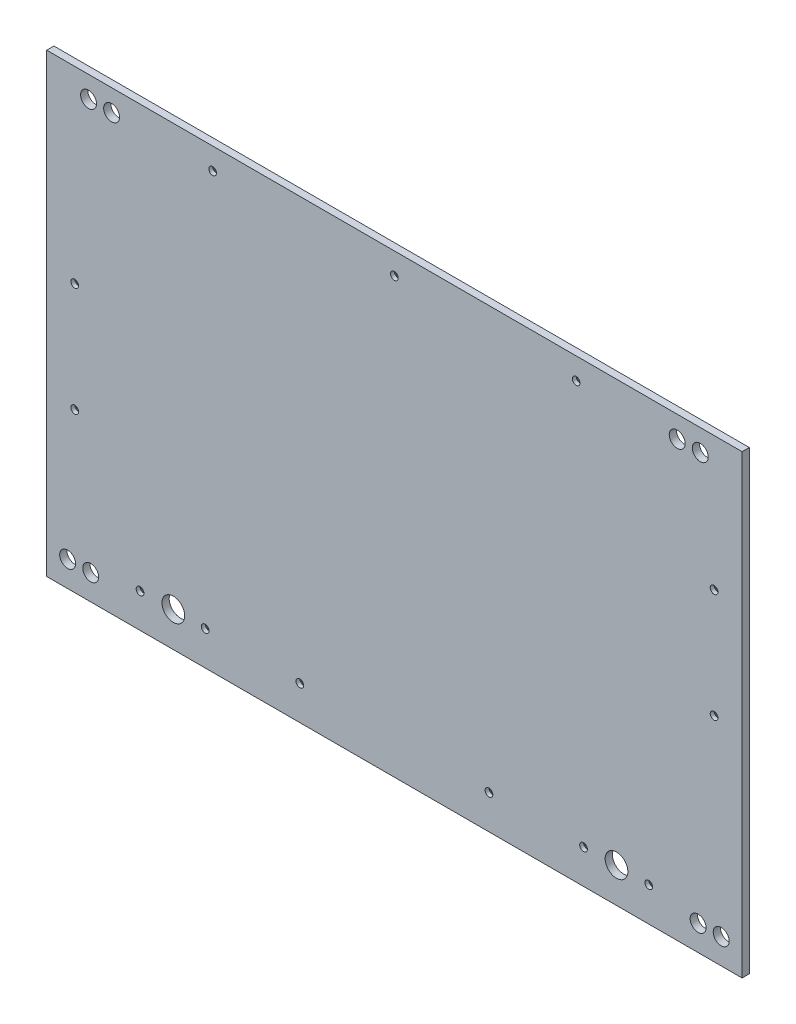
SolidWorks part; units mm, degrees
material "ABS"
ref_plane "X-Y Datum" through (0, 0, 0) normal (0, 0, 1) x (1, 0, 0)
ref_plane "X-Z Datum" through (0, 0, 0) normal (0, 1, 0) x (1, 0, 0)
ref_plane "Y-Z Datum" through (0, 0, 0) normal (1, 0, 0) x (0, 0, -1)
sketch "Sketch1" plane through (0, 0, 0) normal (0, 0, 1) x (1, 0, 0)
  line L0 (-153.025, 98.7125) -> (-153.025, -98.7125)
  line L1 (-153.025, 98.7125) -> (153.025, 98.7125)
  line L2 (-153.025, 98.7125) -> (-153.025, -98.7125)
  line L3 (-153.025, -98.7125) -> (153.025, -98.7125)
  line L4 (153.025, 98.7125) -> (153.025, -98.7125)
  line L5 (-153.025, 98.7125) -> (153.025, -98.7125) construction
  line L6 (-153.025, -98.7125) -> (153.025, 98.7125) construction
  line L7 (-153.025, -98.7125) -> (153.025, -98.7125)
  line L8 (153.025, 98.7125) -> (153.025, -98.7125)
  line L9 (-153.025, 98.7125) -> (153.025, 98.7125)
  circle A0 centre (-142.25, -87.9375) radius 10.775
  circle A1 centre (-118.25, -87.9375) radius 10.775 construction
  circle A2 centre (-130.25, -64.9375) radius 10.775
  point P0 (0, 0)
  dimension "D1" = 21.55
  dimension "D2" = 24
  dimension "D3" = 23
  dimension "D4" = 12
  dimension "D5" = 197.425
  dimension "D6" = 306.05
  dimension "D7" = 0
extrude "Boss-Extrude1" add sketch "Sketch1" along normal blind 3.175 contours A0 L3 L4 L1 L2 A2 | A2 | A0 | A0 L2 L3 | L9 L0 L7 L8 L1 L4 L3 L2 region at (1.7287, 0.9747, 0) region at (-150.6182, -96.3057, 0) region at (-142.25, -87.9375, 0) region at (-130.25, -64.9375, 0)
sketch "Sketch2" plane through (0, 0, 0) normal (0, 0, -1) x (-1, 0, 0)
  circle A1 centre (-97.75, -83.334) radius 5
  circle A2 centre (-97.75, -83.334) radius 5
  circle A8 centre (97.288, -83.334) radius 5 construction
  circle A9 centre (97.288, -83.334) radius 5
  dimension "D1" = 0
extrude "Cut-Extrude1" cut sketch "Sketch2" against normal through all
sketch "Sketch3" plane through (0, 0, 0) normal (0, 0, -1) x (-1, 0, 0)
  circle A0 centre (-124.45, 92.3625) radius 3.5
  circle A1 centre (-134.61, 92.3625) radius 3.5
  circle A2 centre (-133.6575, -87.5375) radius 3.5
  circle A3 centre (-143.8175, -87.5375) radius 3.5
  circle A4 centre (-133.6575, -87.5375) radius 2.75 construction
  circle A5 centre (-133.6575, -87.5375) radius 2.75 construction
  point P0 (-111.94, -83.7125)
  point P1 (-83.25, -83.7125)
  point P3 (-133.6575, -87.5375)
  point P5 (-143.8175, -87.5375)
  point P7 (0, 92.3625)
  point P9 (80, 92.3625)
  point P11 (-124.45, 92.3625)
  point P13 (-134.61, 92.3625)
  point P29 (-41.625, -83.7125)
  point P30 (41.625, -83.7125)
  point P32 (140.6875, -28.9375)
  point P34 (140.6875, 19.0625)
  point P36 (-140.6875, -4.9375)
  point P38 (-140.6875, 43.0625)
  dimension "D1" = 5.5
  dimension "D2" = 7
extrude "Cut-Extrude2" cut sketch "Sketch3" against normal through all
hole_wizard "CSK for M3 Flat Head Machine Screw1" positions "Sketch4" profile "Sketch5" countersink size "M3" standard "ANSI Metric" end condition through all
sketch "Sketch4" plane through (0, 0, 0) normal (0, 0, -1) x (-1, 0, 0)
  point P0 (-111.94, -83.7125)
  point P3 (-83.25, -83.7125)
  point P6 (80, 92.3625)
  point P9 (0, 92.3625)
sketch "Sketch5" plane through (111.94, -83.7125, 0) normal (1, 0, 0) x (0, 1, 0)
  line L0 (0, 0) -> (0, 3.175)
  line L1 (0, 3.175) -> (1.7, 3.175)
  line L2 (1.7, 3.175) -> (1.7, 1.45)
  line L3 (1.7, 1.45) -> (3.15, 0)
  line L5 (3.15, 0) -> (0, 0)
  line L6 (-1.7, 1.45) -> (-3.15, 0) construction
  line L11 (0, -6.35) -> (0, 107.95) construction
  dimension "Thru Hole Dia." = 3.4
  dimension "Thru Hole Depth" = 3.175
  dimension "Near C'Sink Dia." = 6.3
  dimension "Near C'Sink Angle" = 90
mirror "Mirror2" about plane through (0, 0, 0) normal (1, 0, 0) of "Cut-Extrude2", "CSK for M3 Flat Head Machine Screw1"
hole_wizard "CSK for M3 Flat Head Machine Screw2" positions "Sketch7" profile "Sketch8" countersink size "M3" standard "ANSI Metric" end condition through all
sketch "Sketch7" plane through (0, 0, 0) normal (0, 0, -1) x (-1, 0, 0)
  point P0 (-140.6875, 43.0625)
  point P3 (-140.6875, -4.9375)
  point P6 (-41.625, -83.7125)
  point P9 (41.625, -83.7125)
  point P12 (140.6875, -28.9375)
  point P15 (140.6875, 19.0625)
sketch "Sketch8" plane through (140.6875, 43.0625, 0) normal (1, 0, 0) x (0, 1, 0)
  line L0 (0, 0) -> (0, 3.175)
  line L1 (0, 3.175) -> (1.7, 3.175)
  line L2 (1.7, 3.175) -> (1.7, 1.45)
  line L3 (1.7, 1.45) -> (3.15, 0)
  line L5 (3.15, 0) -> (0, 0)
  line L6 (-1.7, 1.45) -> (-3.15, 0) construction
  line L11 (0, -6.35) -> (0, 107.95) construction
  dimension "Thru Hole Dia." = 3.4
  dimension "Thru Hole Depth" = 3.175
  dimension "Near C'Sink Dia." = 6.3
  dimension "Near C'Sink Angle" = 90
sketch "Sketch9" plane through (0, 98.7125, 0) normal (0, 1, 0) x (1, 0, 0)
  line L4 (153.025, 0) -> (-153.025, 0)
  line L5 (-153.025, 0) -> (-153.025, -3.175)
  line L6 (-153.025, -3.175) -> (153.025, -3.175)
  line L7 (153.025, -3.175) -> (153.025, 0)
  line L8 (153.025, 0) -> (-153.025, 0)
  line L9 (-153.025, 0) -> (-153.025, -3.175)
  line L10 (-153.025, -3.175) -> (153.025, -3.175)
  line L11 (153.025, -3.175) -> (153.025, 0)
  dimension "D1" = 0
extrude "Boss-Extrude2" add sketch "Sketch9" along normal blind 3.175
